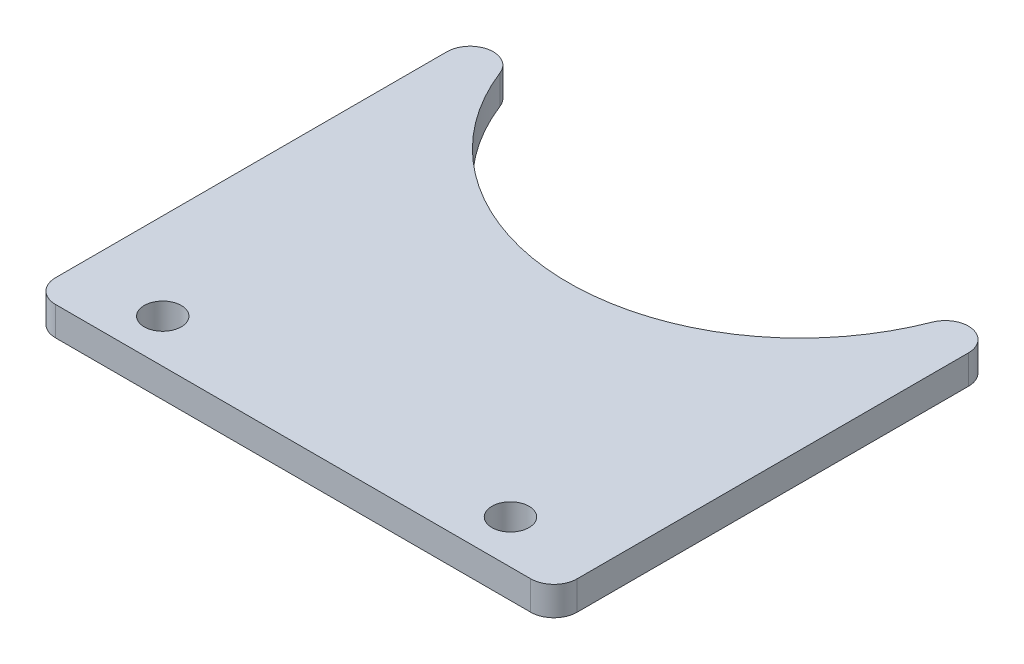
SolidWorks part; units mm, degrees
ref_plane "Front Plane" through (0, 0, 0) normal (0, 0, 1) x (1, 0, 0)
ref_plane "Top Plane" through (0, 0, 0) normal (0, 1, 0) x (1, 0, 0)
ref_plane "Right Plane" through (0, 0, 0) normal (1, 0, 0) x (0, 0, -1)
sketch "Sketch1" plane through (0, 0, 0) normal (0, 1, 0) x (1, 0, 0)
  line L1 (-28.575, 30.1625) -> (28.575, 30.1625)
  line L2 (-28.575, 30.1625) -> (-28.575, -30.1625)
  line L3 (-28.575, -30.1625) -> (28.575, -30.1625)
  line L4 (28.575, 30.1625) -> (28.575, -30.1625)
  line L5 (-28.575, 30.1625) -> (28.575, -30.1625) construction
  line L6 (-28.575, -30.1625) -> (28.575, 30.1625) construction
  point P0 (0, 0)
  dimension "D1" = 57.15
  dimension "D2" = 60.325
extrude "Boss-Extrude1" add sketch "Sketch1" along normal blind 3.175
sketch "Sketch2" plane through (0, 0, 0) normal (0, -1, 0) x (-1, 0, 0)
  line L0 (28.575, -30.1625) -> (-28.575, -30.1625) construction
  line L1 (-19.05, -25.4) -> (-28.575, -25.4) construction
  line L2 (-28.575, -30.1625) -> (-28.575, 30.1625) construction
  line L3 (19.05, -25.4) -> (28.575, -25.4) construction
  line L4 (28.575, 30.1625) -> (28.575, -30.1625) construction
  circle A0 centre (-19.05, -25.4) radius 2.032
  circle A1 centre (19.05, -25.4) radius 2.032
  dimension "D2" = 4.064
  dimension "D1" = 4.7625
  dimension "D3" = 38.1
extrude "Cut-Extrude1" cut sketch "Sketch2" against normal through all
sketch "Sketch3" plane through (0, 0, 0) normal (0, -1, 0) x (1, 0, 0)
  line L1 (-23.9755, -17.0135) -> (-28.575, -30.1625)
  line L2 (23.9755, -17.0135) -> (28.575, -30.1625)
  line L3 (-28.575, -30.1625) -> (28.575, -30.1625)
  arc A0 (23.9755, -17.0135) -> (-23.9755, -17.0135) centre (0, -25.4) ccw
  dimension "D1" = 50.8
  dimension "D2" = 25.4
extrude "Cut-Extrude2" cut sketch "Sketch3" against normal through all
fillet "Fillet1" radius 2.54 2 edges at (-28.575, 1.5875, 30.1625) (28.575, 1.5875, 30.1625)
fillet "Fillet2" radius 2.54 2 edges at (28.575, 1.5875, -30.1625) (-28.575, 1.5875, -30.1625)
